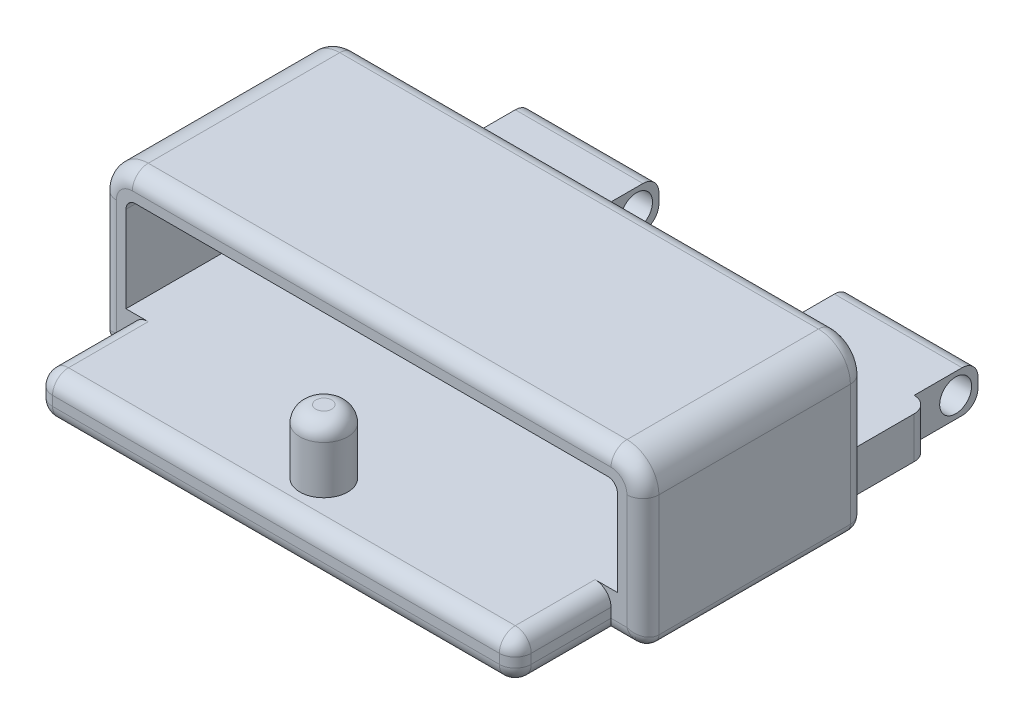
SolidWorks part; units mm, degrees
ref_plane "Front" through (0, 0, 0) normal (0, 0, 1) x (1, 0, 0)
ref_plane "Top" through (0, 0, 0) normal (0, 1, 0) x (1, 0, 0)
ref_plane "Right" through (0, 0, 0) normal (1, 0, 0) x (0, 0, -1)
sketch "Эскиз1" plane through (0, 0, 0) normal (0, 0, 1) x (1, 0, 0)
  line L1 (-7.5, 0.65) -> (7.5, 0.65)
  line L2 (-7.5, 0.65) -> (-7.5, -0.65)
  line L3 (-7.5, -0.65) -> (7.5, -0.65)
  line L4 (7.5, 0.65) -> (7.5, -0.65)
  line L5 (-7.5, 0.65) -> (7.5, -0.65) construction
  line L6 (-7.5, -0.65) -> (7.5, 0.65) construction
  point P0 (0, 0)
  dimension "D1" = 15
  dimension "D2" = 1.3
extrude "Бобышка-Вытянуть1" add sketch "Эскиз1" along normal blind 13
sketch "Эскиз2" plane through (0, 0.65, 0) normal (0, 1, 0) x (1, 0, 0)
  line L0 (-7, 0) -> (-7, 2)
  line L1 (7.5, 0) -> (-7.5, 0) construction
  line L2 (-7, 2) -> (-3, 2)
  line L3 (-3, 2) -> (-3, 0)
  line L4 (-7.5, -13) -> (-7.5, 0) construction
  line L5 (0, 0) -> (0, 13.2692) construction
  line L6 (-7, 0) -> (-3, 0)
  line L7 (7, 0) -> (3, 0)
  line L8 (3, 2) -> (3, 0)
  line L9 (7, 2) -> (3, 2)
  line L10 (7, 0) -> (7, 2)
  dimension "D1" = 4
  dimension "D2" = 0.5
  dimension "D3" = 2
extrude "Бобышка-Вытянуть2" add sketch "Эскиз2" against normal blind 1.3
sketch "Эскиз3" plane through (7, 0, 0) normal (1, 0, 0) x (0, 0, -1)
  line L0 (2, -0.65) -> (2, 0.65) construction
  circle A0 centre (1.3, 0) radius 0.5
  point P2 (2, 0)
  dimension "D1" = 1
  dimension "D2" = 0.7
extrude "Вырез-Вытянуть1" cut sketch "Эскиз3" against normal through all
fillet "Скругление1" radius 0.5 10 edges at (7.5, 0, 13) (-7.5, 0, 13) (-7.5, 0, 0) (7.5, 0, 0) (-5, -0.65, -2) (5, -0.65, -2) (5, 0.65, -2) (-5, 0.65, -2)
ref_plane "Плоскость1" through (0, 0, 3) normal (0, 0, 1) x (1, 0, 0)
sketch "Эскиз4" plane through (0, 0, 3) normal (0, 0, 1) x (1, 0, 0)
  line L0 (-7.5, 0.65) -> (-7.7, 0.65)
  line L1 (-7.7, 0.65) -> (-7.7, 3.35)
  line L2 (-7.4, 3.65) -> (7.4, 3.65)
  line L3 (0, 0) -> (0, 16.6261) construction
  line L4 (-7.5, 0.65) -> (-7.5, -0.65)
  line L5 (-7.5, -0.65) -> (-8.2, -0.65)
  line L6 (-8.5, -0.35) -> (-8.5, 3.45)
  line L7 (-7.5, 4.45) -> (7.5, 4.45)
  line L8 (8.5, -0.35) -> (8.5, 3.45)
  line L9 (7.5, -0.65) -> (8.2, -0.65)
  line L10 (7.5, 0.65) -> (7.5, -0.65)
  line L11 (7.7, 0.65) -> (7.7, 3.35)
  line L12 (7.5, 0.65) -> (7.7, 0.65)
  arc A0 (8.5, 3.45) -> (7.5, 4.45) centre (7.5, 3.45) ccw
  arc A1 (-8.5, 3.45) -> (-7.5, 4.45) centre (-7.5, 3.45) cw
  arc A2 (8.5, -0.35) -> (8.2, -0.65) centre (8.2, -0.35) cw
  arc A3 (-8.2, -0.65) -> (-8.5, -0.35) centre (-8.2, -0.35) cw
  arc A4 (7.7, 3.35) -> (7.4, 3.65) centre (7.4, 3.35) ccw
  arc A5 (-7.7, 3.35) -> (-7.4, 3.65) centre (-7.4, 3.35) cw
  point P14 (0, 4.45)
  point P15 (0, 3.65)
  point P21 (8.5, 4.45)
  point P24 (-8.5, 4.45)
  point P27 (8.5, -0.65)
  point P30 (-8.5, -0.65)
  point P33 (7.7, 3.65)
  point P36 (-7.7, 3.65)
  dimension "D5" = 1
  dimension "D6" = 0.3
  dimension "D1" = 0.2
  dimension "D2" = 3
  dimension "D3" = 1
  dimension "D4" = 0.8
extrude "Бобышка-Вытянуть3" add sketch "Эскиз4" along normal blind 7
fillet "Скругление3" radius 0.5 18 edges at (7.85, -0.65, 10) (8.4121, -0.5621, 10) (8.5, 1.55, 10) (8.2071, 4.1571, 10) (-7.85, -0.65, 10) (-8.4121, -0.5621, 10) (-8.5, 1.55, 10) (-8.2071, 4.1571, 10) (7.85, -0.65, 3) (8.4121, -0.5621, 3) (8.5, 1.55, 3) (8.2071, 4.1571, 3) (-7.85, -0.65, 3) (-8.4121, -0.5621, 3) (-8.5, 1.55, 3) (-8.2071, 4.1571, 3) (0, 4.45, 10) (0, 4.45, 3)
fillet "Скругление4" radius 0.5 10 edges at (-7.5, -0.65, 11) (-7.3536, -0.65, 12.8536) (7.5, -0.65, 11) (7.3536, -0.65, 12.8536) (7.5, 0.65, 11.25) (7.3536, 0.65, 12.8536) (-7.5, 0.65, 11.25) (-7.3536, 0.65, 12.8536) (0, -0.65, 13) (0, 0.65, 13)
sketch "Эскиз5" plane through (0, 0.65, 0) normal (0, 1, 0) x (1, 0, 0)
  line L0 (-7, -12.5) -> (7, -12.5) construction
  circle A0 centre (0, -11.5) radius 0.75
  dimension "D1" = 1.5
  dimension "D2" = 1
extrude "Бобышка-Вытянуть4" add sketch "Эскиз5" along normal blind 2
fillet "Скругление5" radius 0.5 1 edges at (0, 2.65, 12.25)
